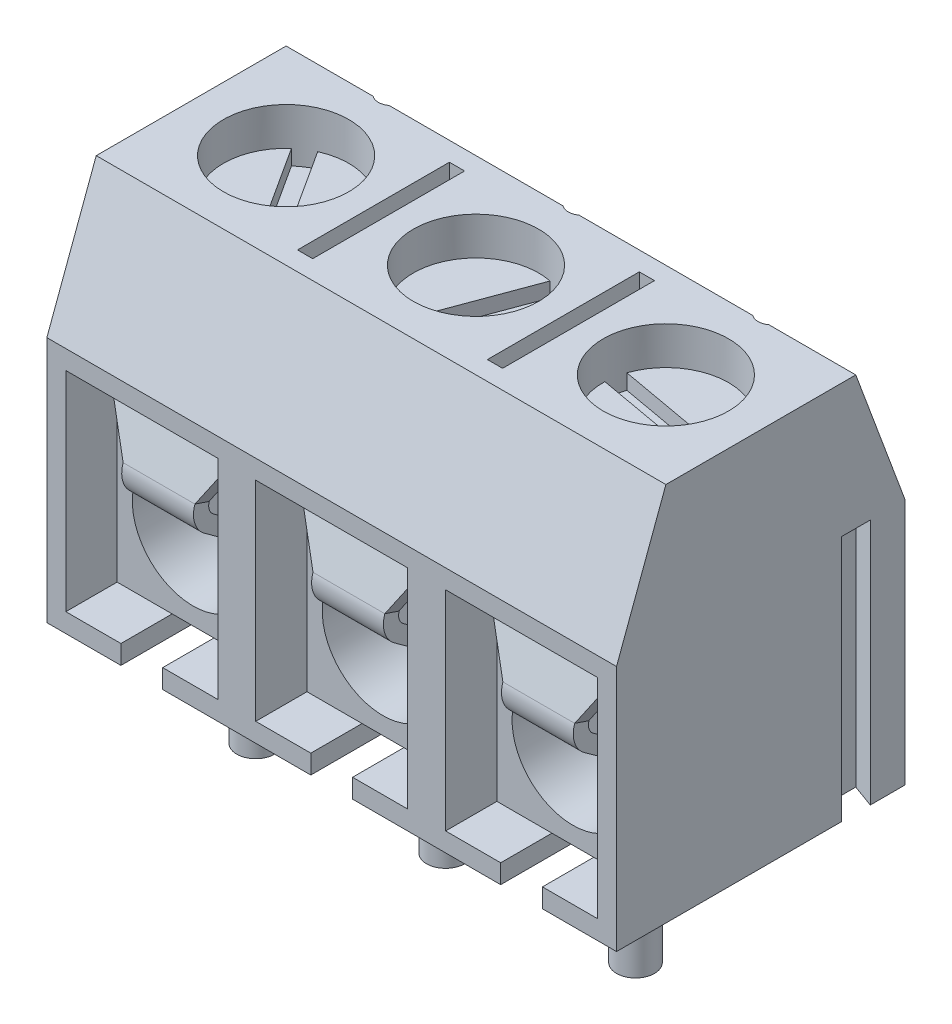
SolidWorks part; units mm, degrees
ref_plane "Front Plane" through (0, 0, 0) normal (0, 0, 1) x (1, 0, 0)
ref_plane "Top Plane" through (0, 0, 0) normal (0, 1, 0) x (1, 0, 0)
ref_plane "Right Plane" through (0, 0, 0) normal (1, 0, 0) x (0, 0, -1)
sketch "Sketch1" plane through (0, 0, 0) normal (0, 1, 0) x (1, 0, 0)
  line L1 (-5, 3.8) -> (10, 3.8)
  line L2 (-5, 3.8) -> (-5, -3.8)
  line L3 (-5, -3.8) -> (10, -3.8)
  line L4 (10, 3.8) -> (10, -3.8)
  dimension "D1" = 15
  dimension "D2" = 5
  dimension "D3" = 7.6
  dimension "D4" = 3.8
extrude "Extrude1" add sketch "Sketch1" along normal blind 10
sketch "Sketch2" plane through (0, 0, 0) normal (1, 0, 0) x (0, 0, -1)
  line L0 (2.5, 10) -> (3.8, 6.5)
  line L1 (3.8, 10) -> (-3.8, 10) construction
  line L2 (3.8, 10) -> (3.8, 0) construction
  line L3 (3.8, 6.5) -> (-3.8, 6.5) construction
  line L4 (-3.8, 10) -> (-3.8, 0) construction
  line L5 (-3.8, 6.5) -> (-2.5, 10)
  line L6 (-2.5, 10) -> (2.5, 10)
  line L7 (3.8, 6.5) -> (3.8, 0)
  line L8 (3.8, 0) -> (-3.8, 0)
  line L9 (-3.8, 0) -> (-3.8, 6.5)
  dimension "D1" = 5
  dimension "D2" = 2.5
  dimension "D3" = 3.5
extrude "Cut-Extrude1" cut sketch "Sketch2" against normal through all and the other way through all flip side to cut
sketch "Sketch3" plane through (0, 10, 0) normal (0, 1, 0) x (-1, 0, 0)
  line L0 (5, -2.5) -> (-10, -2.5) construction
  line L1 (0.2, -2) -> (-0.2, -2)
  line L2 (0.2, -2) -> (0.2, 2)
  line L3 (0.2, 2) -> (-0.2, 2)
  line L4 (-0.2, -2) -> (-0.2, 2)
  line L5 (-4.8, -2) -> (-5.2, -2)
  line L6 (-4.8, -2) -> (-4.8, 2)
  line L7 (-4.8, 2) -> (-5.2, 2)
  line L8 (-5.2, -2) -> (-5.2, 2)
  line L9 (-5, -2) -> (-5, 2) construction
  circle A0 centre (2.5, 0) radius 1.65
  circle A1 centre (-2.5, 0) radius 1.65
  circle A2 centre (2.5, -2.78) radius 0.35
  circle A3 centre (-2.5, -2.78) radius 0.35
  circle A4 centre (-7.5, 0) radius 1.65
  circle A5 centre (-7.5, -2.78) radius 0.35
  dimension "D7" = 3.3
  dimension "D8" = 0.7
  dimension "D1" = 0.4
  dimension "D2" = 0.2
  dimension "D3" = 4
  dimension "D4" = 2
  dimension "D5" = 2.5
  dimension "D6" = 2.5
  dimension "D9" = 0.28
  dimension "D10" = 0.4
  dimension "D11" = 4
  dimension "D12" = 5
  dimension "D13" = 5
extrude "Cut-Extrude2" cut sketch "Sketch3" against normal blind 4
sketch "Sketch4" plane through (0, 0, 3.8) normal (0, 0, 1) x (1, 0, 0)
  line L0 (-5, 6.5) -> (-5, 0) construction
  line L1 (-4.5, 6) -> (-0.5, 6)
  line L2 (-4.5, 6) -> (-4.5, 0.5)
  line L3 (-4.5, 0.5) -> (-0.5, 0.5)
  line L4 (-0.5, 6) -> (-0.5, 0.5)
  line L5 (0.5, 6) -> (4.5, 6)
  line L6 (0.5, 6) -> (0.5, 0.5)
  line L7 (0.5, 0.5) -> (4.5, 0.5)
  line L8 (4.5, 6) -> (4.5, 0.5)
  line L9 (-5, 6.5) -> (10, 6.5) construction
  line L10 (-5, 0) -> (10, 0) construction
  line L12 (10, 6.5) -> (10, 0) construction
  line L13 (5.5, 6) -> (9.5, 6)
  line L14 (5.5, 6) -> (5.5, 0.5)
  line L15 (5.5, 0.5) -> (9.5, 0.5)
  line L16 (9.5, 6) -> (9.5, 0.5)
  dimension "D1" = 0.5
  dimension "D2" = 0.5
  dimension "D3" = 0.5
  dimension "D4" = 1
  dimension "D5" = 0.5
  dimension "D6" = 1
extrude "Cut-Extrude3" cut sketch "Sketch4" against normal offset from surface (5.6 mm away) 2 up to face at (2.5, 3.25, -3.8)
sketch "Sketch7" plane through (0, 0, 0) normal (0, 1, 0) x (1, 0, 0)
  line L0 (-5, 2.5) -> (-5, -2.5) construction
  line L1 (-5.6, 3.1) -> (-5, 2.8816)
  line L2 (-5.6, 3.1) -> (-5.6, 1.9)
  line L3 (-5.6, 1.9) -> (-5, 2.1184)
  line L4 (-5, 2.8816) -> (-5, 2.1184)
  line L5 (10, 3.8) -> (-5, 3.8) construction
  dimension "D1" = 1.2
  dimension "D2" = 70
  dimension "D3" = 70
  dimension "D4" = 0.6
  dimension "D5" = 1.9
extrude "Extrude3" add sketch "Sketch7" along normal up to vertex (6.5 mm away) up to point (-5, 6.5, -3.8)
sketch "Sketch9" plane through (0, 0, 0) normal (0, 1, 0) x (1, 0, 0)
  line L0 (10, -3.8) -> (10, 3.8) construction
  line L8 (10, 2.8816) -> (9.4, 3.1)
  line L9 (10, 2.1184) -> (10, 2.8816)
  line L10 (9.4, 1.9) -> (10, 2.1184)
  line L11 (9.4, 3.1) -> (9.4, 1.9)
  dimension "D1" = 0.6
extrude "Cut-Extrude5" cut sketch "Sketch9" along normal up to vertex (6.5 mm away) up to point (10, 6.5, -3.8)
sketch "Sketch10" plane through (0, 0, 3.8) normal (0, 0, 1) x (1, 0, 0)
  line L1 (-3.05, 0.5) -> (-1.95, 0.5)
  line L2 (-3.05, 0.5) -> (-3.05, 0)
  line L3 (-3.05, 0) -> (-1.95, 0)
  line L4 (-1.95, 0.5) -> (-1.95, 0)
  line L5 (-5, 0) -> (10, 0) construction
  line L7 (1.95, 0.5) -> (3.05, 0.5)
  line L8 (1.95, 0.5) -> (1.95, 0)
  line L9 (1.95, 0) -> (3.05, 0)
  line L10 (3.05, 0.5) -> (3.05, 0)
  line L11 (6.95, 0.5) -> (8.05, 0.5)
  line L12 (6.95, 0.5) -> (6.95, 0)
  line L13 (6.95, 0) -> (8.05, 0)
  line L14 (8.05, 0.5) -> (8.05, 0)
  line L15 (-4.5, 0.5) -> (-0.5, 0.5) construction
  dimension "D1" = 1.1
  dimension "D4" = 1.1
extrude "Cut-Extrude6" cut sketch "Sketch10" against normal blind 3.6
sketch "Sketch5" plane through (0, 0, -1.8) normal (0, 0, 1) x (1, 0, 0)
  line L0 (-4.5, 5.6) -> (-0.5, 5.6)
  line L1 (0.5, 5.6) -> (4.5, 5.6)
  line L2 (-4.5, 5.6) -> (-4.5, 0.5)
  line L3 (-0.5, 5.6) -> (-0.5, 6) construction
  line L4 (-4.5, 6) -> (-4.5, 0.5)
  line L5 (-4.5, 0.5) -> (-0.5, 0.5)
  line L6 (-0.5, 0.5) -> (-0.5, 6)
  line L7 (-0.5, 6) -> (-4.5, 6)
  line L8 (-4.5, 6) -> (-4.5, 5.6) construction
  line L9 (-4.5, 0.5) -> (-0.5, 0.5)
  line L10 (-0.5, 0.5) -> (-0.5, 5.6)
  line L11 (-0.5, 6) -> (-4.5, 6) construction
  line L12 (0.5, 6) -> (0.5, 0.5)
  line L13 (0.5, 0.5) -> (4.5, 0.5)
  line L14 (4.5, 0.5) -> (4.5, 6)
  line L15 (4.5, 6) -> (0.5, 6)
  line L16 (0.5, 6) -> (0.5, 5.6) construction
  line L17 (0.5, 0.5) -> (4.5, 0.5)
  line L18 (4.5, 0.5) -> (4.5, 5.6)
  line L19 (4.5, 6) -> (0.5, 6) construction
  line L20 (0.5, 5.6) -> (0.5, 0.5)
  line L21 (4.5, 5.6) -> (4.5, 6) construction
  line L22 (5.5, 5.6) -> (9.5, 5.6)
  line L23 (5.5, 5.6) -> (5.5, 0.5)
  line L24 (9.5, 5.6) -> (9.5, 6) construction
  line L26 (5.5, 6) -> (5.5, 0.5)
  line L27 (5.5, 0.5) -> (9.5, 0.5)
  line L28 (9.5, 0.5) -> (9.5, 6)
  line L29 (9.5, 6) -> (5.5, 6)
  line L30 (5.5, 6) -> (5.5, 5.6) construction
  line L31 (5.5, 0.5) -> (9.5, 0.5)
  line L32 (9.5, 0.5) -> (9.5, 5.6)
  line L33 (9.5, 6) -> (5.5, 6) construction
  dimension "D3" = 0.4
  dimension "D1" = 0
  dimension "D2" = 0
  dimension "D4" = 0
extrude "Extrude2" add sketch "Sketch5" along normal offset from surface (4.25 mm away) 1.35 up to face at (2.5, 1.9643, 3.8)
sketch "Sketch6" plane through (0, 0, 2.45) normal (0, 0, 1) x (1, 0, 0)
  circle A0 centre (-2.5, 2.5543) radius 1.6
  circle A1 centre (2.5, 2.5543) radius 1.6
  circle A2 centre (7.5, 2.5543) radius 1.6
  dimension "D1" = 3.2
  dimension "D2" = 5
  dimension "D3" = 5
extrude "Cut-Extrude4" cut sketch "Sketch6" against normal up to surface (4.25 mm away) up to face at (-2.5, 5.8, -1.8)
ref_plane "Plane1" through (-2.5, 0, 0) normal (1, 0, 0) x (0, 0, -1)
ref_plane "Plane2" through (2.5, 0, 0) normal (1, 0, 0) x (0, 0, -1)
sketch "Sketch11" plane through (0, 0.5, 0) normal (0, -1, 0) x (1, 0, 0)
  line L0 (-2.5, -1.8) -> (-2.5, 2.45) construction
  line L1 (2.5, -1.8) -> (2.5, 2.45) construction
  line L2 (-3.05, 0.2) -> (-1.95, 0.2) construction
  line L3 (7.5, -1.8) -> (7.5, 2.45) construction
  circle A0 centre (-2.5, 0.8) radius 0.5
  circle A1 centre (2.5, 0.8) radius 0.5
  circle A2 centre (7.5, 0.8) radius 0.5
  dimension "D1" = 0.6
extrude "Extrude4" add sketch "Sketch11" along normal blind 3.5
sketch "Sketch12" plane through (0, 6, 0) normal (0, -1, 0) x (1, 0, 0)
  circle A0 centre (2.5, 0) radius 1.65 construction
  circle A1 centre (-2.5, 0) radius 1.65 construction
  circle A2 centre (2.5, 0) radius 1.65
  circle A3 centre (-2.5, 0) radius 1.65
  circle A4 centre (7.5, 0) radius 1.65 construction
  circle A5 centre (7.5, 0) radius 1.65
extrude "Extrude5" add sketch "Sketch12" against normal offset from surface (3 mm away) 1 up to face at (2.5, 10, -1.479)
sketch "Sketch13" plane through (0, 9, 0) normal (0, 1, 0) x (-1, 0, 0)
  line L1 (3.5943, -1.2349) -> (1.8258, 1.506)
  line L2 (3.1742, -1.506) -> (1.4057, 1.2349)
  line L3 (-5.9389, -0.5343) -> (-9.1495, 0.0421)
  line L4 (-5.8505, -0.0421) -> (-9.0611, 0.5343)
  line L5 (-2.8322, -1.6162) -> (-1.699, 1.4425)
  line L6 (-3.301, -1.4425) -> (-2.1678, 1.6162)
  circle A0 centre (-2.5, 0) radius 1.65 construction
  circle A1 centre (2.5, 0) radius 1.65 construction
  arc A2 (-1.699, 1.4425) -> (-2.1678, 1.6162) centre (-2.5, 0) ccw
  arc A3 (1.8258, 1.506) -> (1.4057, 1.2349) centre (2.5, 0) ccw
  arc A4 (-3.301, -1.4425) -> (-2.8322, -1.6162) centre (-2.5, 0) ccw
  arc A5 (3.1742, -1.506) -> (3.5943, -1.2349) centre (2.5, 0) ccw
  circle A6 centre (-7.5, 0) radius 1.65 construction
  arc A7 (-5.9389, -0.5343) -> (-5.8505, -0.0421) centre (-7.5, 0) ccw
  arc A8 (-9.0611, 0.5343) -> (-9.1495, 0.0421) centre (-7.5, 0) ccw
  dimension "D1" = 0.5
  dimension "D2" = 0.5
  dimension "D3" = 0.5
extrude "Cut-Extrude7" cut sketch "Sketch13" against normal blind 0.4
sketch "Sketch14" plane through (-2.5, 0, 0) normal (-1, 0, 0) x (0, 0, 1)
  line L0 (2.45, 5.6) -> (3.0389, 3.8617)
  line L1 (3.0389, 3.8617) -> (0.1672, 1.7876)
  line L2 (0.1672, 1.7876) -> (-0.5464, 2.0974)
  line L3 (-0.5464, 2.0974) -> (-0.7057, 1.7305)
  line L4 (-0.7057, 1.7305) -> (0.2168, 1.33)
  line L5 (0.2168, 1.33) -> (3.5125, 3.7103)
  line L6 (-1.8, 5.6) -> (2.45, 5.6)
  line L7 (-1.8, 5.6) -> (2.45, 5.6)
  line L8 (2.45, 0.5) -> (3.8, 0.5)
  line L9 (3.8, 0.5) -> (3.8, 6)
  line L10 (3.8, 6) -> (-1.8, 6)
  line L11 (-1.8, 6) -> (-1.8, 5.6)
  line L12 (2.45, 5.6) -> (2.45, 0.5)
  line L13 (3.5125, 3.7103) -> (2.7368, 6)
  line L14 (2.7368, 6) -> (-1.8, 6)
  line L17 (-1.8, 6) -> (-1.8, 5.6)
  dimension "D2" = 0.4
  dimension "D3" = 0.4
  dimension "D4" = 0.4
  dimension "D1" = 0
extrude "Extrude6" add sketch "Sketch14" along normal blind 0.945 and the other way blind 0.945
sketch "Sketch15" plane through (0, 1.4494, 4.2784) normal (0, 0.3209, 0.9471) x (1, 0, 0)
  line L2 (-1.555, 4.8) -> (-1.555, 2.904)
  line L3 (-3.445, 4.8) -> (-3.445, 2.904)
  line L4 (-1.555, 2.904) -> (-0.51, 4.8)
  line L5 (-0.51, 4.8) -> (-1.555, 4.8)
  line L6 (-3.445, 2.904) -> (-4.49, 4.8)
  line L8 (-4.49, 4.8) -> (-3.445, 4.8)
extrude "Extrude9" add sketch "Sketch15" against normal blind 0.39
pattern_linear "LPattern1" count 3 spacing 5 along (1, 0, 0) of "Extrude6", "Extrude9"
fillet "Fillet1" radius 0.3 6 edges at (-2.5, 3.8617, 3.0389) (-2.5, 1.7876, 0.1672) (2.5, 1.7876, 0.1672) (2.5, 3.8617, 3.0389) (7.5, 1.7876, 0.1672) (7.5, 3.8617, 3.0389)
fillet "Fillet2" radius 0.7 6 edges at (-2.5, 3.7103, 3.5125) (-2.5, 1.33, 0.2168) (2.5, 1.33, 0.2168) (2.5, 3.7103, 3.5125) (7.5, 3.7103, 3.5125) (7.5, 1.33, 0.2168)
sketch "Component_Outline" plane through (0, 0, 0) normal (0, 1, 0) x (1, 0, 0)
  line L0 (10, -3.8) -> (-5, -3.8)
  line L1 (-5, -3.8) -> (-5, 2.1184)
  line L2 (-5, 2.1184) -> (-5.6, 1.9)
  line L3 (-5.6, 1.9) -> (-5.6, 3.1)
  line L4 (-5.6, 3.1) -> (-5, 2.8816)
  line L5 (-5, 2.8816) -> (-5, 3.8)
  line L6 (-5, 3.8) -> (10, 3.8)
  line L7 (10, 3.8) -> (10, -3.8)
  line L8 (-5, -3.8) -> (10, 3.8) construction
  point P4 (2.5, 0)
